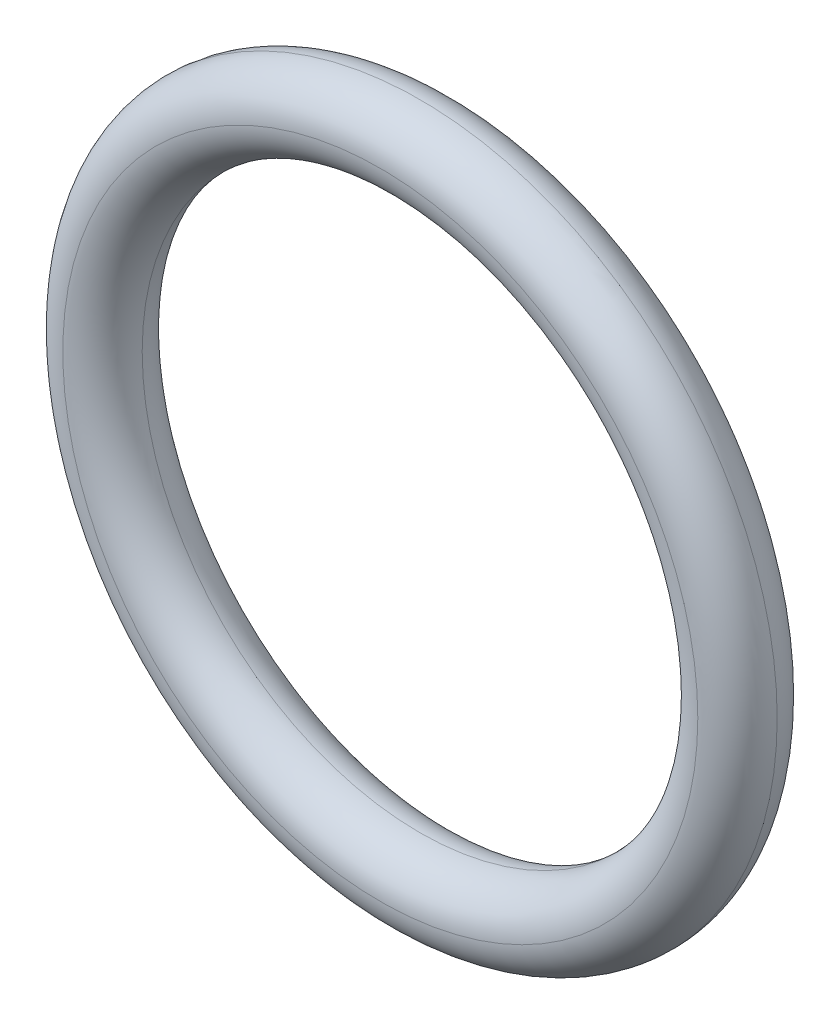
SolidWorks part; units mm, degrees
material "VITON"
ref_plane "Front" through (0, 0, 0) normal (0, 0, 1) x (1, 0, 0)
ref_plane "Top" through (0, 0, 0) normal (0, 1, 0) x (1, 0, 0)
ref_plane "Right" through (0, 0, 0) normal (1, 0, 0) x (0, 0, -1)
sketch "Sketch1" plane through (0, 0, 0) normal (0, 0, 1) x (1, 0, 0)
  circle A0 centre (0, 0) radius 9
extrude "Boss-Extrude1" add sketch "Sketch1" along normal blind 2
sketch "Sketch2" plane through (0, 0, 2) normal (0, 0, 1) x (1, 0, 0)
  circle A0 centre (0, 0) radius 7
extrude "Cut-Extrude1" cut sketch "Sketch2" against normal blind 2
fillet "Fillet1" radius 1 4 edges at (7, 0, 2) (7, 0, 0) (9, 0, 0) (9, 0, 2)
